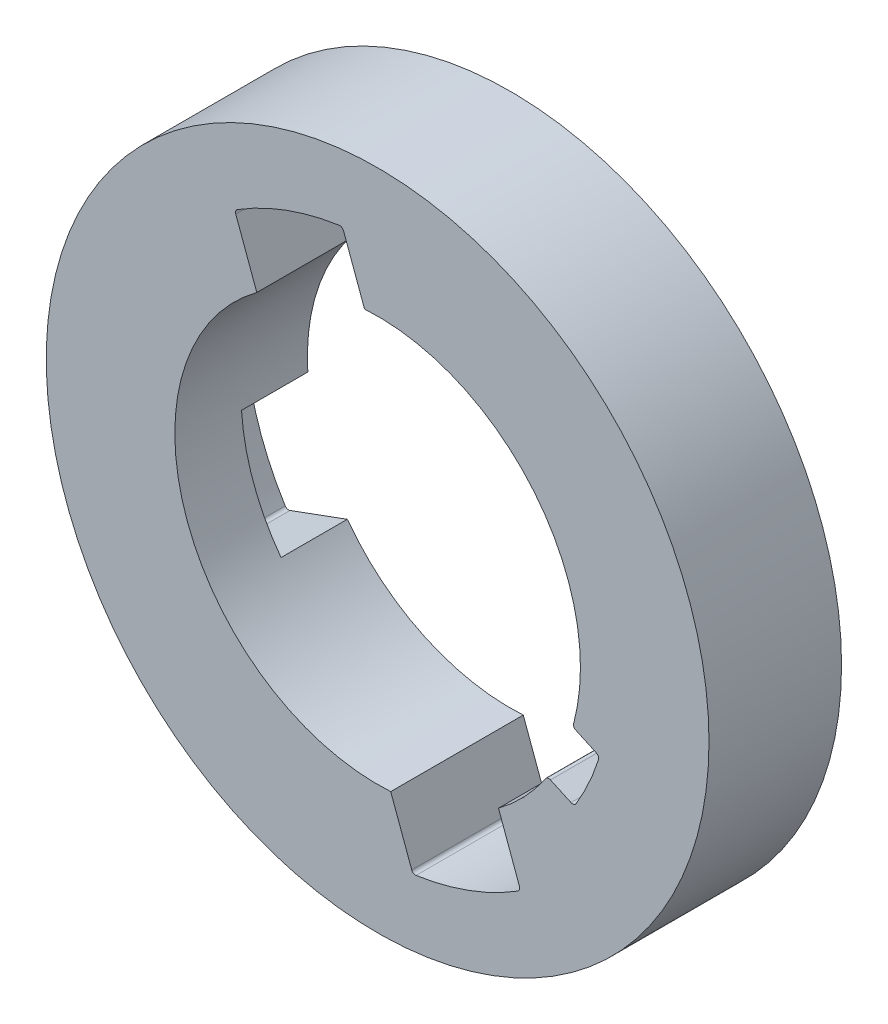
SolidWorks part; units mm, degrees
material "Chêne"
ref_plane "Plan de face" through (0, 0, 0) normal (0, 0, 1) x (1, 0, 0)
ref_plane "Plan de dessus" through (0, 0, 0) normal (0, 1, 0) x (1, 0, 0)
ref_plane "Plan de droite" through (0, 0, 0) normal (1, 0, 0) x (0, 0, -1)
sketch "Esquisse1" plane through (0, 0, 0) normal (0, 0, 1) x (1, 0, 0)
  line L0 (14.953, -4.2772) -> (16.5018, -4.9824)
  line L1 (13.0383, -8.4787) -> (14.587, -9.1845)
  line L2 (10.7023, -16.615) -> (9.1158, -12.2879)
  line L3 (19.5952, 2.5738) -> (15.2681, 0.9873)
  line L4 (16.615, 10.7023) -> (12.2879, 9.1158)
  line L5 (2.5738, -19.5952) -> (0.9873, -15.2681)
  line L6 (-16.615, -10.7023) -> (-12.2879, -9.1158)
  line L7 (-19.5952, -2.5738) -> (-15.2681, -0.9873)
  line L8 (-10.7023, 16.615) -> (-9.1158, 12.2879)
  line L9 (-2.5738, 19.5952) -> (-0.9873, 15.2681)
  arc A0 (12.6655, -8.5834) -> (14.7874, -3.9272) centre (0, 0) cw
  arc A1 (16.6631, -5.3471) -> (14.968, -9.0669) centre (0, 0) cw
  arc A2 (14.953, -4.2772) -> (14.7874, -3.9272) centre (15.0774, -4.0042) cw
  arc A3 (16.6631, -5.3471) -> (16.5018, -4.9824) centre (16.3774, -5.2555) ccw
  arc A4 (14.587, -9.1845) -> (14.968, -9.0669) centre (14.7114, -8.9115) ccw
  circle A5 centre (0, 0) radius 25
  arc A6 (19.5952, 2.5738) -> (19.7888, 2.8989) centre (19.492, 2.8555) ccw
  arc A7 (19.7888, 2.8989) -> (16.9729, 10.5793) centre (0, 0) ccw
  arc A8 (16.9729, 10.5793) -> (16.615, 10.7023) centre (16.7183, 10.4206) ccw
  arc A9 (10.5793, -16.9729) -> (10.7023, -16.615) centre (10.4206, -16.7183) ccw
  arc A10 (2.8989, -19.7888) -> (10.5793, -16.9729) centre (0, 0) ccw
  arc A11 (2.5738, -19.5952) -> (2.8989, -19.7888) centre (2.8555, -19.492) ccw
  arc A12 (-16.9729, -10.5793) -> (-16.615, -10.7023) centre (-16.7183, -10.4206) ccw
  arc A13 (-19.7888, -2.8989) -> (-16.9729, -10.5793) centre (0, 0) ccw
  arc A14 (-19.5952, -2.5738) -> (-19.7888, -2.8989) centre (-19.492, -2.8555) ccw
  arc A15 (-10.5793, 16.9729) -> (-10.7023, 16.615) centre (-10.4206, 16.7183) ccw
  arc A16 (-2.8989, 19.7888) -> (-10.5793, 16.9729) centre (0, 0) ccw
  arc A17 (-2.5738, 19.5952) -> (-2.8989, 19.7888) centre (-2.8555, 19.492) ccw
  arc A18 (13.0383, -8.4787) -> (12.6655, -8.5834) centre (12.9139, -8.7517) ccw
extrude "Boss.-Extru.1" add sketch "Esquisse1" along normal blind 10 contours A5 L1 A18 A0 L2 A9 A10 A11 L5 L6 A12 A13 A14 L7 L8 A15 A16 A17 L9 L4 A8 A7 A6 L3 A2 L0 A3 A1 A4 | A7 A8 L4 A0 L3 A6 | L7 A14 A13 A12 L6 A0 region at (16.398, 6.0121, 0) region at (-16.398, -6.0121, 0) region at (-24.2929, 0, 0)
extrude "Enlèv. mat.-Extru.1" cut sketch "Esquisse1<6>" along normal blind 5 contours A7 A8 L4 A0 L3 A6 | L7 A14 A13 A12 L6 A0 region at (16.398, 6.0121, 0) region at (-16.398, -6.0121, 0)
sketch "Esquisse1<6>" plane through (0, 0, 0) normal (0, 0, 1) x (1, 0, 0) same geometry as "Esquisse1"
